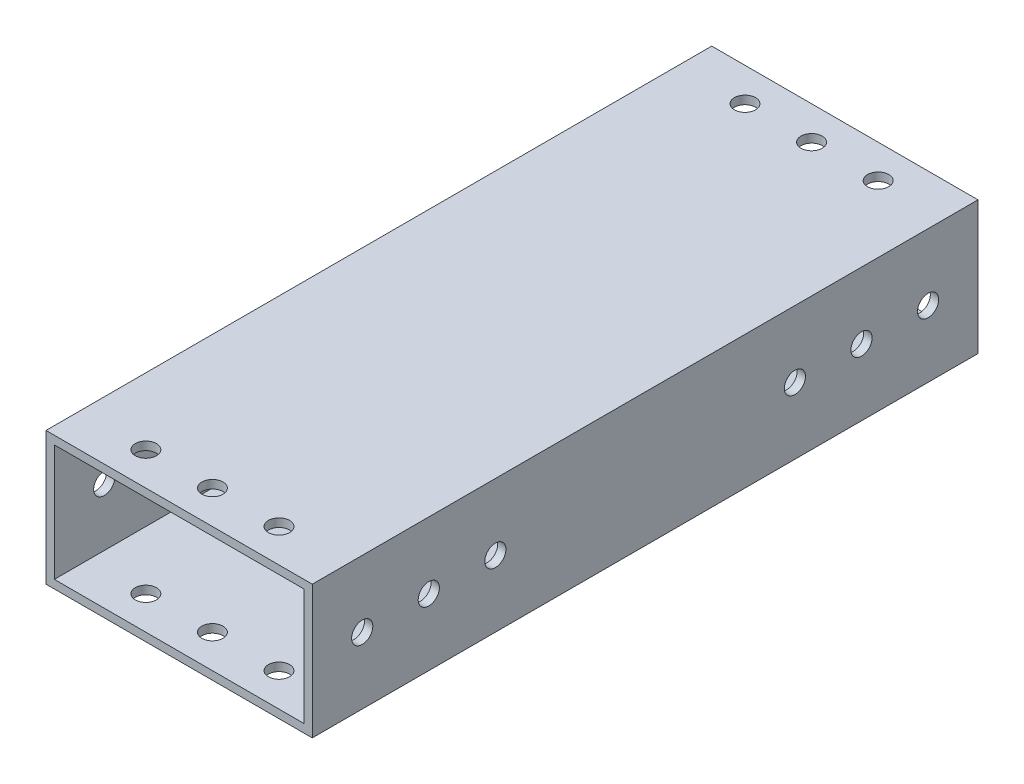
SolidWorks part; units mm, degrees
material "6061-T6 (SS)"
ref_plane "Front Plane" through (0, 0, 0) normal (0, 0, 1) x (1, 0, 0)
ref_plane "Top Plane" through (0, 0, 0) normal (0, 1, 0) x (1, 0, 0)
ref_plane "Right Plane" through (0, 0, 0) normal (1, 0, 0) x (0, 0, -1)
sketch "Sketch1" plane through (0, 0, 0) normal (0, 0, 1) x (1, 0, 0)
  line L0 (-23.8125, 11.1125) -> (23.8125, 11.1125)
  line L1 (-25.4, -12.7) -> (25.4, -12.7)
  line L2 (-25.4, -12.7) -> (-25.4, 12.7)
  line L3 (-25.4, 12.7) -> (25.4, 12.7)
  line L4 (25.4, -12.7) -> (25.4, 12.7)
  line L5 (-25.4, -12.7) -> (25.4, 12.7) construction
  line L6 (-25.4, 12.7) -> (25.4, -12.7) construction
  line L7 (23.8125, -11.1125) -> (23.8125, 11.1125)
  line L8 (-23.8125, -11.1125) -> (23.8125, -11.1125)
  line L9 (-23.8125, -11.1125) -> (-23.8125, 11.1125)
  point P0 (0, 0)
  dimension "D1" = 50.8
  dimension "D2" = 25.4
  dimension "D3" = 1.5875
extrude "Boss-Extrude1" add sketch "Sketch1" along normal mid plane 127
sketch "Sketch2" plane through (0, 12.7, 0) normal (0, 1, 0) x (1, 0, 0)
  line L0 (25.4, 63.5) -> (-25.4, 63.5) construction
  line L1 (25.4, 0) -> (-25.4, 0) construction
  line L2 (25.4, -63.5) -> (25.4, 63.5) construction
  line L3 (-25.4, -63.5) -> (-25.4, 63.5) construction
  circle A0 centre (-12.7, 57.15) radius 2.0193
  circle A1 centre (0, 57.15) radius 2.0193
  circle A2 centre (12.7, 57.15) radius 2.0193
  circle A3 centre (12.7, -57.15) radius 2.0193
  circle A4 centre (0, -57.15) radius 2.0193
  circle A5 centre (-12.7, -57.15) radius 2.0193
  dimension "D4" = 4.0386
  dimension "D1" = 12.7
  dimension "D2" = 12.7
  dimension "D3" = 6.35
extrude "Cut-Extrude1" cut sketch "Sketch2" against normal through all
sketch "Sketch3" plane through (-25.4, 0, 0) normal (-1, 0, 0) x (0, 0, 1)
  line L0 (-63.5, 12.7) -> (-63.5, -12.7) construction
  line L1 (0, 12.7) -> (0, -12.7) construction
  line L2 (63.5, 12.7) -> (-63.5, 12.7) construction
  line L3 (63.5, -12.7) -> (-63.5, -12.7) construction
  circle A0 centre (-53.975, 0) radius 2.0193
  circle A1 centre (53.975, 0) radius 2.0193
  circle A2 centre (-41.275, 0) radius 2.0193
  circle A3 centre (-28.575, 0) radius 2.0193
  circle A4 centre (28.575, 0) radius 2.0193
  circle A5 centre (41.275, 0) radius 2.0193
  point P17 (0, 0)
  point P18 (0, 0)
  dimension "D1" = 4.0386
  dimension "D3" = 4.0386
  dimension "D2" = 9.525
  dimension "D4" = 12.7
  dimension "D5" = 12.7
extrude "Cut-Extrude2" cut sketch "Sketch3" against normal through all
